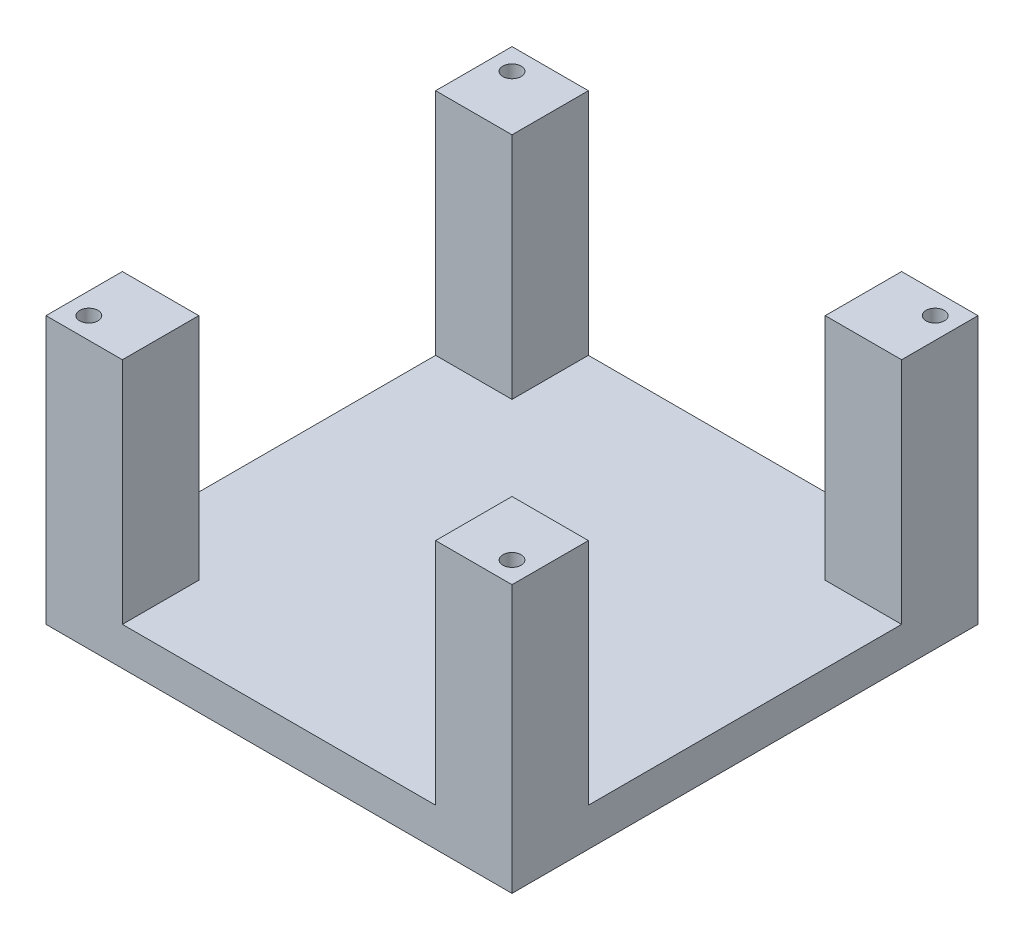
SolidWorks part; units mm, degrees
ref_plane "Front Plane" through (0, 0, 0) normal (0, 0, 1) x (1, 0, 0)
ref_plane "Top Plane" through (0, 0, 0) normal (0, 1, 0) x (1, 0, 0)
ref_plane "Right Plane" through (0, 0, 0) normal (1, 0, 0) x (0, 0, -1)
sketch "Sketch3" plane through (0, 0, 0) normal (0, 1, 0) x (1, 0, 0)
  line L1 (-77.47, -77.47) -> (77.47, -77.47)
  line L2 (-77.47, -77.47) -> (-77.47, 77.47)
  line L3 (-77.47, 77.47) -> (77.47, 77.47)
  line L4 (77.47, -77.47) -> (77.47, 77.47)
  line L5 (-77.47, -77.47) -> (77.47, 77.47) construction
  line L6 (-77.47, 77.47) -> (77.47, -77.47) construction
  point P0 (0, 0)
  dimension "D1" = 154.94
  dimension "D2" = 154.94
extrude "Boss-Extrude3" add sketch "Sketch3" along normal mid plane 12.7
sketch "Sketch4" plane through (0, 6.35, 0) normal (0, 1, 0) x (1, 0, 0)
  line L0 (0, 77.47) -> (0, -77.47) construction
  line L1 (-77.47, 77.47) -> (-52.07, 77.47)
  line L2 (-77.47, 77.47) -> (-77.47, 52.07)
  line L3 (-77.47, 52.07) -> (-52.07, 52.07)
  line L4 (-52.07, 77.47) -> (-52.07, 52.07)
  line L5 (77.47, 77.47) -> (-77.47, 77.47) construction
  line L6 (-77.47, -77.47) -> (77.47, -77.47) construction
  line L7 (77.47, 0) -> (-77.47, 0) construction
  line L8 (77.47, -77.47) -> (77.47, 77.47) construction
  line L9 (-77.47, 77.47) -> (-77.47, -77.47) construction
  line L10 (52.07, 77.47) -> (52.07, 52.07)
  line L11 (77.47, 52.07) -> (52.07, 52.07)
  line L12 (77.47, 77.47) -> (77.47, 52.07)
  line L13 (77.47, 77.47) -> (52.07, 77.47)
  line L14 (77.47, -77.47) -> (52.07, -77.47)
  line L15 (77.47, -77.47) -> (77.47, -52.07)
  line L16 (77.47, -52.07) -> (52.07, -52.07)
  line L17 (52.07, -77.47) -> (52.07, -52.07)
  line L18 (-52.07, -77.47) -> (-52.07, -52.07)
  line L19 (-77.47, -52.07) -> (-52.07, -52.07)
  line L20 (-77.47, -77.47) -> (-77.47, -52.07)
  line L21 (-77.47, -77.47) -> (-52.07, -77.47)
  dimension "D1" = 25.4
extrude "Boss-Extrude4" add sketch "Sketch4" along normal blind 76.2
sketch "Sketch5" plane through (0, 82.55, 0) normal (0, 1, 0) x (1, 0, 0)
  circle A0 centre (70.3501, 70.3501) radius 3.04 construction
  circle A1 centre (-70.3501, 70.3501) radius 3.04 construction
  circle A2 centre (-70.3501, -70.3501) radius 3.04 construction
  circle A3 centre (70.3501, -70.3501) radius 3.04 construction
  circle A4 centre (70.3501, 70.3501) radius 3.04
  circle A5 centre (-70.3501, 70.3501) radius 3.04
  circle A6 centre (-70.3501, -70.3501) radius 3.04
  circle A7 centre (70.3501, -70.3501) radius 3.04
extrude "Cut-Extrude1" cut sketch "Sketch5" against normal blind 19.05
